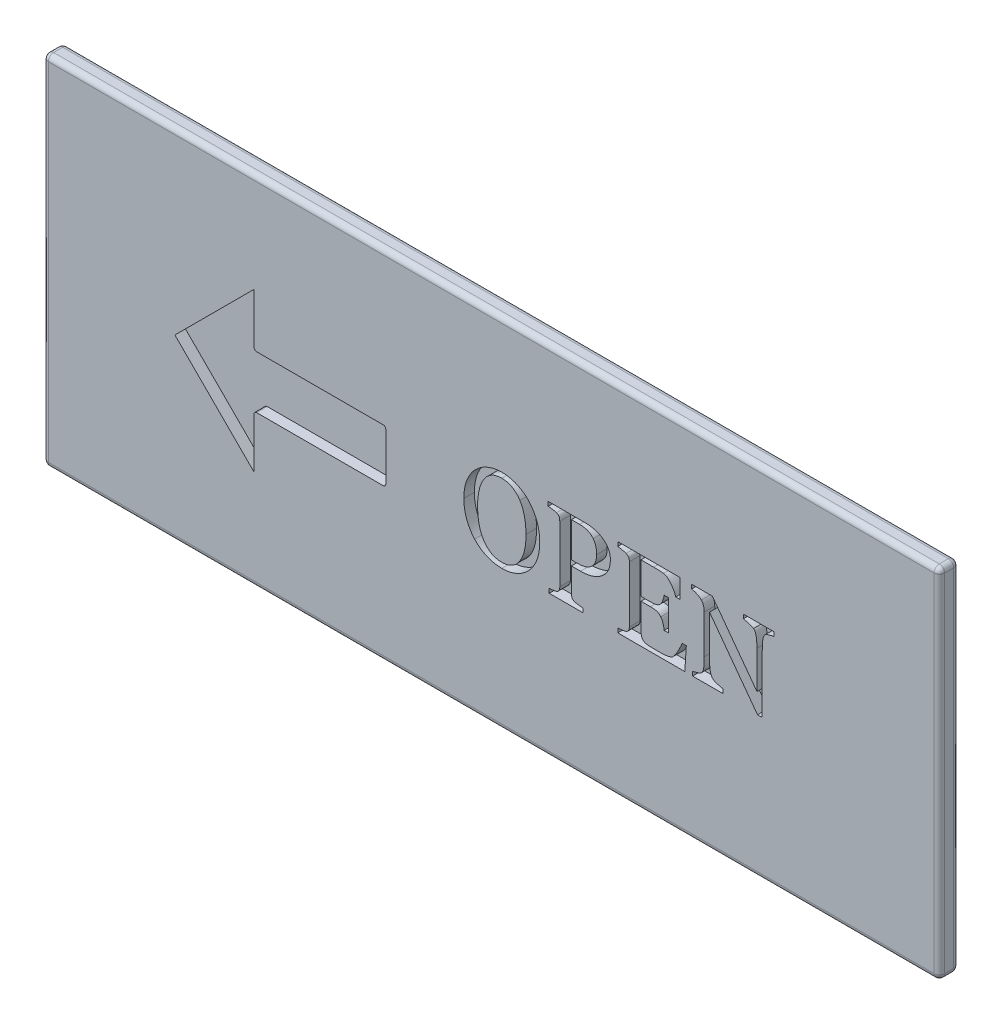
SolidWorks part; units mm, degrees
ref_plane "前视基准面" through (0, 0, 0) normal (0, 0, 1) x (1, 0, 0)
ref_plane "上视基准面" through (0, 0, 0) normal (0, 1, 0) x (1, 0, 0)
ref_plane "右视基准面" through (0, 0, 0) normal (1, 0, 0) x (0, 0, -1)
other "Configuration Table"
sketch "草图1" plane through (0, 0, 0) normal (0, 0, 1) x (1, 0, 0)
  line L1 (85, -33.9) -> (-85, -33.9)
  line L2 (85, -33.9) -> (85, 33.9)
  line L3 (85, 33.9) -> (-85, 33.9)
  line L4 (-85, -33.9) -> (-85, 33.9)
  line L5 (85, -33.9) -> (-85, 33.9) construction
  line L6 (85, 33.9) -> (-85, -33.9) construction
  point P0 (0, 0)
  dimension "D1" = 170
  dimension "D2" = 67.8
extrude "凸台-拉伸1" add sketch "草图1" along normal blind 3.7
fillet "圆角1" radius 1 12 edges at (0, -33.9, 3.7) (0, -33.9, 0) (0, 33.9, 3.7) (0, 33.9, 0) (-85, 33.9, 1.85) (-85, 0, 3.7) (-85, -33.9, 1.85) (-85, 0, 0) (85, -33.9, 1.85) (85, 0, 3.7) (85, 33.9, 1.85) (85, 0, 0)
sketch "草图2" plane through (0, 0, 3.7) normal (0, 0, 1) x (1, 0, 0)
  line L1 (84, -33.9) -> (-84, -33.9) construction
  line L6 (-45, -15) -> (-60, 0)
  line L7 (-60, 0) -> (-45, 15)
  line L8 (-45, 15) -> (-45, -15)
  line L9 (-85, -32.9) -> (-85, 32.9) construction
  line L10 (-45, 5) -> (-20, 5)
  line L11 (-45, 5) -> (-45, -5)
  line L12 (-45, -5) -> (-20, -5)
  line L13 (-20, 5) -> (-20, -5)
  point P15 (-45, 0)
  point P16 (-45, 0)
  dimension "D1" = 18.9
  dimension "D2" = 90
  dimension "D3" = 15
  dimension "D4" = 25
  dimension "D5" = 25
  dimension "D6" = 10
extrude "切除-拉伸1" cut sketch "草图2" against normal blind 2 contours L13 L10 L8 L12 | L8 L7 L6 region at (-50, 0, 3.7) region at (-32.5, 0, 3.7)
sketch "草图3" plane through (0, 0, 3.7) normal (0, 0, 1) x (1, 0, 0)
  line L0 (-37, -6.9301) -> (85, -6.9301) construction
  line L1 (85, 32.9) -> (85, -32.9) construction
  line L2 (-85, -32.9) -> (-85, 32.9) construction
  text T0 "OPEN" font "Georgia" height 15
  point P3 (85, -10.1287)
  point P6 (-40.9579, -10.9579)
  point P7 (-37.7899, -6.9301)
  point P8 (0, 0)
  dimension "D1" = 48
extrude "切除-拉伸2" cut sketch "草图3" against normal blind 2
fillet "圆角2" radius 0.5 4 edges at (-20, -5, 2.7) (-20, 5, 2.7) (-45, -5, 2.7) (-45, 5, 2.7)
